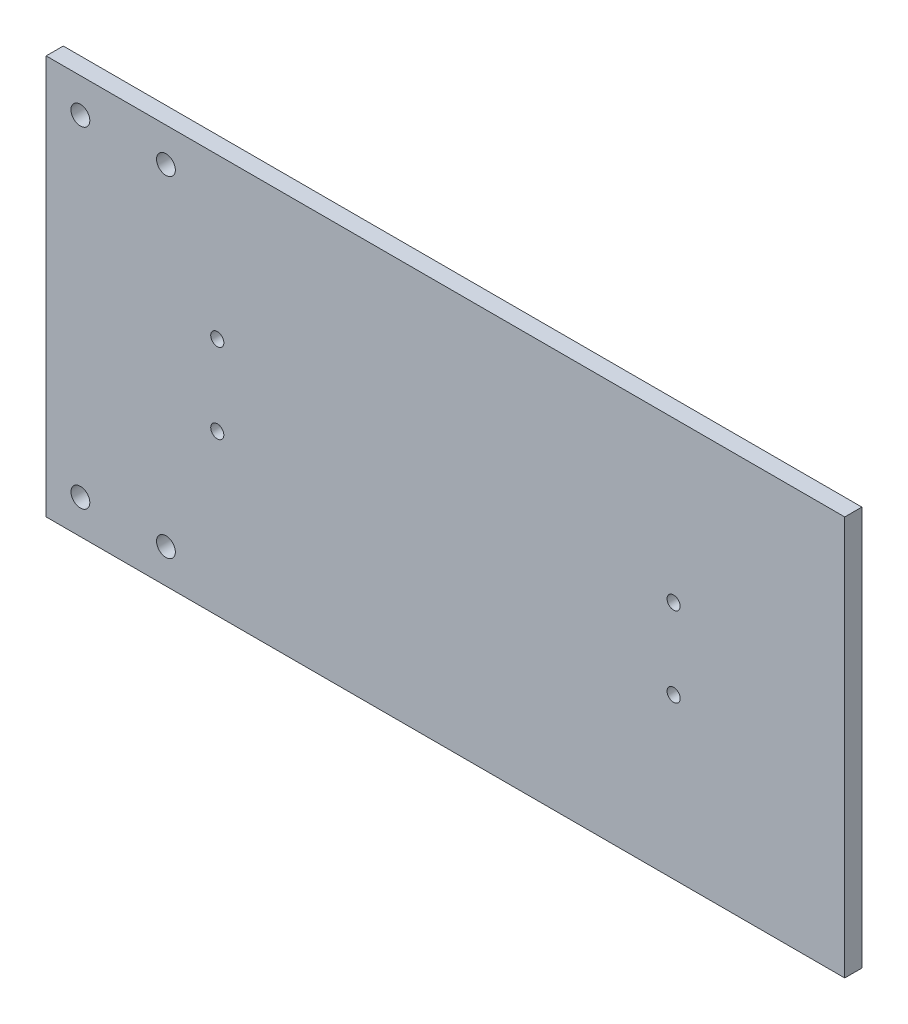
SolidWorks part; units mm, degrees
ref_plane "前视基准面" through (0, 0, 0) normal (0, 0, 1) x (1, 0, 0)
ref_plane "上视基准面" through (0, 0, 0) normal (0, 1, 0) x (1, 0, 0)
ref_plane "右视基准面" through (0, 0, 0) normal (1, 0, 0) x (0, 0, -1)
sketch "草图1" plane through (0, 0, 0) normal (0, 0, 1) x (1, 0, 0)
  line L1 (-70, -35) -> (70, -35)
  line L2 (-70, -35) -> (-70, 35)
  line L3 (-70, 35) -> (70, 35)
  line L4 (70, -35) -> (70, 35)
  line L5 (-70, -35) -> (70, 35) construction
  line L6 (-70, 35) -> (70, -35) construction
  point P0 (0, 0)
  dimension "D1" = 140
  dimension "D2" = 70
extrude "凸台-拉伸1" add sketch "草图1" along normal blind 3
sketch "草图2" plane through (0, 0, 0) normal (0, 0, -1) x (-1, 0, 0)
  line L0 (49, 29) -> (64, 29) construction
  line L1 (64, 29) -> (64, -29) construction
  line L2 (64, -29) -> (49, -29) construction
  line L3 (49, -29) -> (49, 29) construction
  line L4 (70, 35) -> (70, -35) construction
  circle A0 centre (64, 29) radius 1.65
  circle A1 centre (64, -29) radius 1.65
  circle A2 centre (49, 29) radius 1.65
  circle A3 centre (49, -29) radius 1.65
  point P8 (64, 0)
  point P11 (70, 0)
  dimension "D4" = 3.3
  dimension "D1" = 15
  dimension "D2" = 58
  dimension "D3" = 6
extrude "切除-拉伸1" cut sketch "草图2" against normal through all
sketch "草图3" plane through (0, 0, 0) normal (0, 0, -1) x (-1, 0, 0)
  line L0 (-40, 7) -> (40, 7) construction
  line L1 (40, 7) -> (40, -7) construction
  line L2 (40, -7) -> (-40, -7) construction
  line L3 (-40, -7) -> (-40, 7) construction
  circle A0 centre (-40, 7) radius 1.15
  circle A1 centre (-40, -7) radius 1.15
  circle A2 centre (40, 7) radius 1.15
  circle A3 centre (40, -7) radius 1.15
  point P8 (40, 0)
  point P9 (0, 7)
  dimension "D1" = 2.3
  dimension "D2" = 80
  dimension "D3" = 14
extrude "切除-拉伸2" cut sketch "草图3" against normal through all
